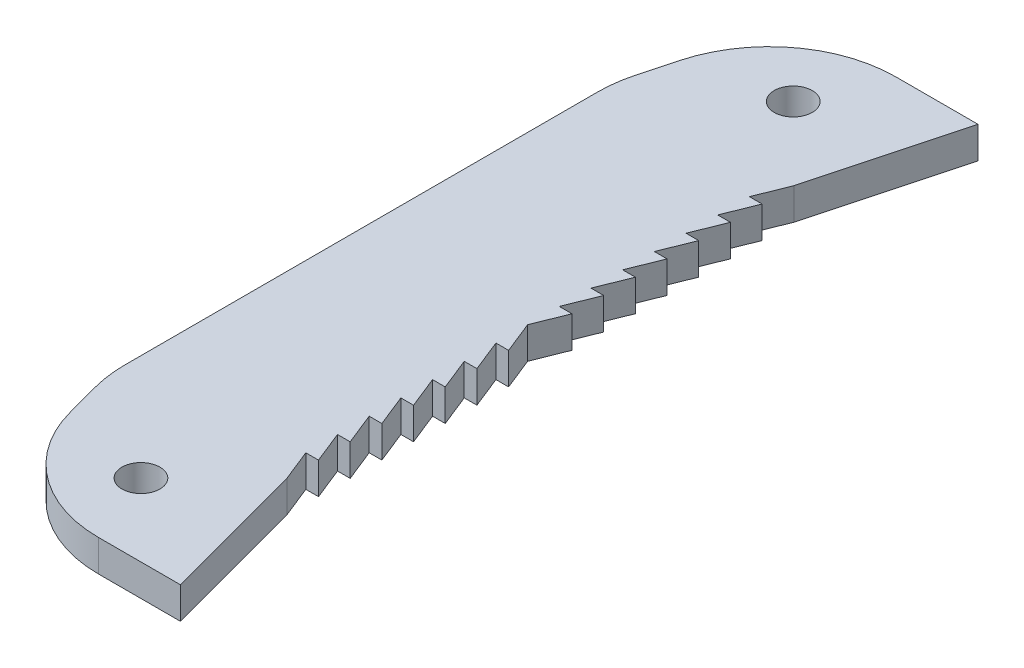
SolidWorks part; units mm, degrees
material "Maple"
ref_plane "Front Plane" through (0, 0, 0) normal (0, 0, 1) x (1, 0, 0)
ref_plane "Top Plane" through (0, 0, 0) normal (0, 1, 0) x (1, 0, 0)
ref_plane "Right Plane" through (0, 0, 0) normal (1, 0, 0) x (0, 0, -1)
sketch "Sketch1" plane through (0, 0, 0) normal (0, 1, 0) x (1, 0, 0)
  line L0 (-15, -15) -> (-43.2843, -43.2843) construction
  line L1 (-11.4645, -18.5355) -> (-39.7487, -46.8198) construction
  line L2 (-18.5355, -11.4645) -> (-46.8198, -39.7487) construction
  line L3 (0, 40.0167) -> (0, -40.0167) construction
  line L4 (46.0662, 0) -> (-46.0662, 0) construction
  line L5 (-18.5355, -11.4645) -> (-21.6074, 0)
  line L6 (-21.6074, 0) -> (-21.6074, 40)
  line L7 (-4.3934, -11.4645) -> (-7.4653, 0)
  line L8 (-18.5355, -11.4645) -> (-46.8198, -39.7487) construction
  line L9 (-39.7487, -46.8198) -> (-4.3934, -11.4645)
  line L10 (-7.4653, 0) -> (-7.4653, 20) construction
  line L11 (-8.4653, 20) -> (-8.4653, 0) construction
  line L12 (-8.4653, 0) -> (-7.4653, 0) construction
  line L13 (-7.4653, 0) -> (-8.4653, 2.5)
  line L14 (-8.4653, 2.5) -> (-7.4653, 2.5)
  line L15 (-7.4653, 2.5) -> (-8.4653, 5)
  line L16 (-8.4653, 5) -> (-7.4653, 5)
  line L17 (-7.4653, 5) -> (-8.4653, 7.5)
  line L18 (-8.4653, 7.5) -> (-7.4653, 7.5)
  line L19 (-7.4653, 7.5) -> (-8.4653, 10)
  line L20 (-8.4653, 10) -> (-7.4653, 10)
  line L21 (-7.4653, 10) -> (-8.4653, 12.5)
  line L22 (-8.4653, 12.5) -> (-7.4653, 12.5)
  line L23 (-7.4653, 12.5) -> (-8.4653, 15)
  line L24 (-8.4653, 15) -> (-7.4653, 15)
  line L25 (-7.4653, 15) -> (-8.4653, 17.5)
  line L26 (-8.4653, 17.5) -> (-7.4653, 17.5)
  line L27 (-7.4653, 17.5) -> (-8.4653, 20)
  line L28 (-8.4653, 20) -> (-7.4653, 20)
  line L29 (-46.3507, 20) -> (0, 20) construction
  line L31 (-7.4653, 22.5) -> (-8.4653, 20)
  line L32 (-8.4653, 22.5) -> (-7.4653, 22.5)
  line L33 (-7.4653, 25) -> (-8.4653, 22.5)
  line L34 (-8.4653, 25) -> (-7.4653, 25)
  line L35 (-7.4653, 27.5) -> (-8.4653, 25)
  line L36 (-8.4653, 27.5) -> (-7.4653, 27.5)
  line L37 (-7.4653, 30) -> (-8.4653, 27.5)
  line L38 (-8.4653, 30) -> (-7.4653, 30)
  line L39 (-7.4653, 32.5) -> (-8.4653, 30)
  line L40 (-8.4653, 32.5) -> (-7.4653, 32.5)
  line L41 (-7.4653, 35) -> (-8.4653, 32.5)
  line L42 (-8.4653, 35) -> (-7.4653, 35)
  line L43 (-7.4653, 37.5) -> (-8.4653, 35)
  line L44 (-8.4653, 37.5) -> (-7.4653, 37.5)
  line L45 (-7.4653, 40) -> (-8.4653, 37.5)
  line L46 (-4.3934, 51.4645) -> (-7.4653, 40)
  line L47 (-18.5355, 51.4645) -> (-21.6074, 40)
  line L48 (-18.5355, -11.4645) -> (-46.8198, -39.7487)
  line L49 (-4.3934, 51.4645) -> (-18.5355, 51.4645)
  line L50 (-4.3934, -11.4645) -> (-18.5355, -11.4645)
  arc A0 (-11.4645, -18.5355) -> (-18.5355, -11.4645) centre (-15, -15) ccw construction
  arc A1 (-46.8198, -39.7487) -> (-39.7487, -46.8198) centre (-43.2843, -43.2843) ccw construction
  arc A2 (-46.8198, -39.7487) -> (-39.7487, -46.8198) centre (-43.2843, -43.2843) ccw
  circle A3 centre (-43.2843, -43.2843) radius 1.5
  circle A5 centre (-25.6066, -25.6066) radius 1.5
  circle A9 centre (-13.2415, -5.7322) radius 1.5
  circle A11 centre (-13.2415, 45.7322) radius 1.5
  point P2 (-29.1421, -29.1421)
  point P58 (-21.6074, 20)
  point P62 (-20.0715, -5.7322)
  dimension "D2" = 5
  dimension "D11" = 3
  dimension "D14" = 3
  dimension "D1" = 40
  dimension "D3" = 45
  dimension "D4" = 15
  dimension "D5" = 15
  dimension "D6" = 120
  dimension "D7" = 1
  dimension "D9" = 20
  dimension "D10" = 2.5
  dimension "D12" = 25
  dimension "D13" = 14.1421
  dimension "D16" = 6.83
  dimension "D17" = 13.6603
  dimension "D8" = 8
extrude "Boss-Extrude1" [suppressed] add sketch "Sketch1" along normal mid plane 2.5 contours L48 A2 L9 L7 L13 L14 L15 L16 L17 L18 L19 L20 L21 L22 L23 L24 L25 L26 L27 L31 L32 L33 L34 L35 L36 L37 L38 L39 L40 L41 L42 L43 L44 L45 L46 L49 L47 L6 L5 A5 A3 | L48 A2 L9 L50 A5 A3
extrude "Boss-Extrude2" add sketch "Sketch1<3>" along normal blind 2.5 contours L50 L7 L13 L14 L15 L16 L17 L18 L19 L20 L21 L22 L23 L24 L25 L26 L27 L31 L32 L33 L34 L35 L36 L37 L38 L39 L40 L41 L42 L43 L44 L45 L46 L49 L47 L6 L5 A9 A11 region at (-14.1332, 0, -20)
sketch "Sketch1<3>" plane through (0, 0, 0) normal (0, 1, 0) x (1, 0, 0) same geometry as "Sketch1"
fillet "Fillet1" radius 10 4 edges at (-18.5355, 1.25, 11.4645) (-21.6074, 1.25, 0) (-21.6074, 1.25, -40) (-18.5355, 1.25, -51.4645)
fillet "Fillet2" [suppressed] radius 10
